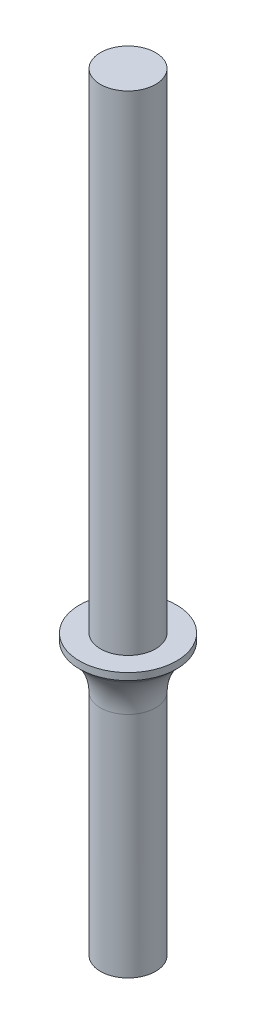
SolidWorks part; units mm, degrees
material "PVC 0.007 Plasticized"
ref_plane "Front Plane" through (0, 0, 0) normal (0, 0, 1) x (1, 0, 0)
ref_plane "Top Plane" through (0, 0, 0) normal (0, 1, 0) x (1, 0, 0)
ref_plane "Right Plane" through (0, 0, 0) normal (1, 0, 0) x (0, 0, -1)
sketch "Sketch1" plane through (0, 0, 0) normal (0, 1, 0) x (1, 0, 0)
  circle A0 centre (0, 0) radius 3.95
  dimension "D1" = 7.9
extrude "Boss-Extrude1" add sketch "Sketch1" along normal blind 110
ref_plane "Plane1" through (0, 55, 0) normal (0, 1, 0) x (1, 0, 0)
ref_plane "Plane2" through (0, 39, 0) normal (0, -1, 0) x (-1, 0, 0)
sketch "Sketch2" plane through (0, 39, 0) normal (0, -1, 0) x (-1, 0, 0)
  circle A0 centre (0, 0) radius 6.95
  circle A1 centre (0, 0) radius 3.95 construction
  dimension "D1" = 3
extrude "Boss-Extrude2" add sketch "Sketch2" against normal blind 1
chamfer "Chamfer1" distance 3 angle 45 1 edges at (0, 39, -3.95)
fillet "Fillet1" radius 8 1 edges at (0, 36, -3.95)
